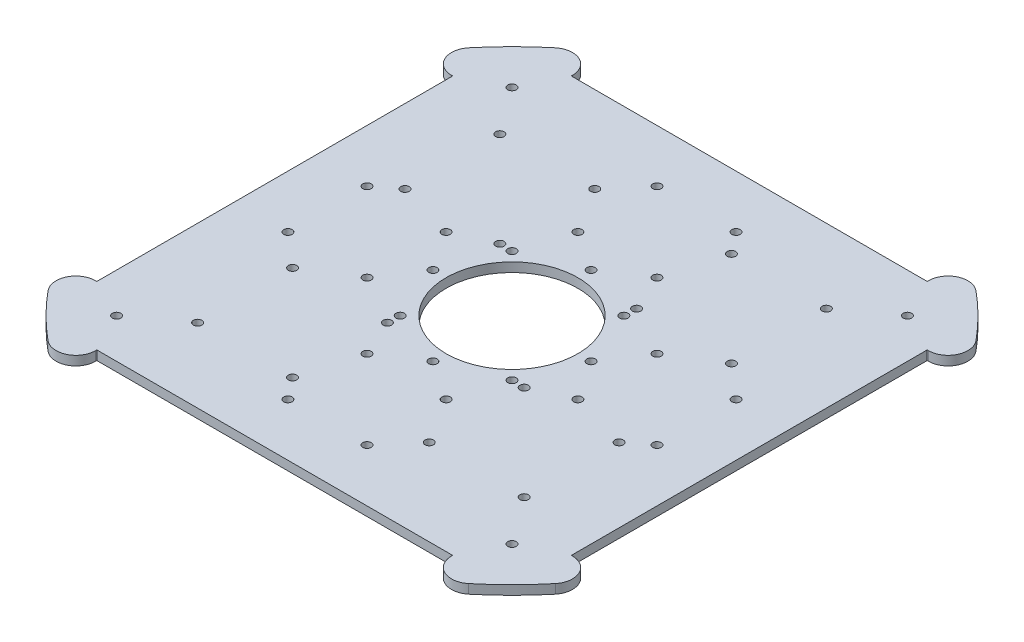
SolidWorks part; units mm, degrees
ref_plane "Front Plane" through (0, 0, 0) normal (0, 0, 1) x (1, 0, 0)
ref_plane "Top Plane" through (0, 0, 0) normal (0, 1, 0) x (1, 0, 0)
ref_plane "Right Plane" through (0, 0, 0) normal (1, 0, 0) x (0, 0, -1)
sketch "Sketch1" plane through (0, 0, 0) normal (0, 1, 0) x (1, 0, 0)
  line L0 (135, 67.5) -> (90, 67.5)
  line L5 (-67.5, 135) -> (67.5, 135)
  line L6 (-67.5, 135) -> (-67.5, 90)
  line L7 (-67.5, 90) -> (67.5, 90)
  line L8 (67.5, 135) -> (67.5, 90)
  line L9 (135, 67.5) -> (135, -67.5)
  line L10 (135, -67.5) -> (90, -67.5)
  line L11 (90, 67.5) -> (90, -67.5)
  line L12 (67.5, -135) -> (67.5, -90)
  line L13 (67.5, -135) -> (-67.5, -135)
  line L14 (-67.5, -135) -> (-67.5, -90)
  line L15 (67.5, -90) -> (-67.5, -90)
  line L16 (-135, -67.5) -> (-90, -67.5)
  line L17 (-135, -67.5) -> (-135, 67.5)
  line L18 (-135, 67.5) -> (-90, 67.5)
  line L19 (-90, -67.5) -> (-90, 67.5)
  line L20 (0, 125) -> (0, 90) construction
  line L21 (0, 135) -> (0, 125) construction
  circle A0 centre (0, 0) radius 125
  point P7 (0, 90)
  point P23 (0, 0)
  dimension "D1" = 250
  dimension "D4" = 35
  dimension "D2" = 135
  dimension "D5" = 10
  dimension "D3" = 4
extrude "Boss-Extrude1" add sketch "Sketch1" along normal blind 3.5 contours L12 A0 L10 L11 L0 L8 L7 L6 L18 L19 L16 L14 L15 region at (0, 0, 0)
fillet "Fillet1" radius 7.5 8 edges at (-105.2081, 1.75, 67.5) (-105.2081, 1.75, -67.5) (-67.5, 1.75, -105.2081) (67.5, 1.75, -105.2081) (105.2081, 1.75, -67.5) (105.2081, 1.75, 67.5) (67.5, 1.75, 105.2081) (-67.5, 1.75, 105.2081)
sketch "Sketch3" plane through (0, 3.5, 0) normal (0, 1, 0) x (1, 0, 0)
  line L0 (0, -90) -> (0, -55) construction
  line L1 (67.5, -90) -> (-67.5, -90) construction
  line L2 (-15, -70) -> (15, -70) construction
  line L3 (-90, 0) -> (-55, 0) construction
  line L4 (-70, 15) -> (-70, -15) construction
  line L5 (0, 90) -> (0, 55) construction
  line L6 (15, 70) -> (-15, 70) construction
  line L7 (90, 0) -> (55, 0) construction
  line L8 (70, -15) -> (70, 15) construction
  line L9 (-90, -67.5) -> (-90, 67.5) construction
  circle A0 centre (-15, -70) radius 1.6
  circle A1 centre (-15, -40) radius 1.6
  circle A2 centre (15, -40) radius 1.6
  circle A3 centre (15, -70) radius 1.6
  circle A4 centre (-40, 15) radius 1.6
  circle A5 centre (-40, -15) radius 1.6
  circle A6 centre (-70, -15) radius 1.6
  circle A7 centre (-70, 15) radius 1.6
  circle A8 centre (15, 40) radius 1.6
  circle A9 centre (-15, 40) radius 1.6
  circle A10 centre (-15, 70) radius 1.6
  circle A11 centre (15, 70) radius 1.6
  circle A12 centre (40, -15) radius 1.6
  circle A13 centre (40, 15) radius 1.6
  circle A14 centre (70, 15) radius 1.6
  circle A15 centre (70, -15) radius 1.6
  point P7 (0, -70)
  point P16 (0, -55)
  point P48 (0, 0)
  dimension "D1" = 3.2
  dimension "D2" = 30
  dimension "D3" = 35
  dimension "D4" = 4
  dimension "D5" = 4
extrude "Cut-Extrude2" cut sketch "Sketch3" against normal through all both and the other way through all
sketch "Sketch4" plane through (0, 3.5, 0) normal (0, 1, 0) x (1, 0, 0)
  circle A0 centre (0, 0) radius 25
  circle A1 centre (0, 30) radius 1.6
  circle A2 centre (21.2132, 21.2132) radius 1.6
  circle A3 centre (30, 0) radius 1.6
  circle A4 centre (21.2132, -21.2132) radius 1.6
  circle A5 centre (0, -30) radius 1.6
  circle A6 centre (-21.2132, -21.2132) radius 1.6
  circle A7 centre (-30, 0) radius 1.6
  circle A8 centre (-21.2132, 21.2132) radius 1.6
  point P22 (0, 0)
  dimension "D1" = 50
  dimension "D2" = 3.2
  dimension "D3" = 30
  dimension "D4" = 8
extrude "Cut-Extrude3" cut sketch "Sketch4" against normal through all both and the other way through all
sketch "Sketch5" plane through (0, 3.5, 0) normal (0, 1, 0) x (1, 0, 0)
  line L0 (75, -75) -> (88.3883, -88.3883) construction
  line L1 (-75, -75) -> (-88.3883, -88.3883) construction
  line L2 (-90, 0) -> (90, 0) construction
  line L3 (-90, -67.5) -> (-90, 67.5) construction
  line L4 (90, 67.5) -> (90, -67.5) construction
  circle A0 centre (75, -75) radius 1.6
  circle A1 centre (-75, -75) radius 1.6
  arc A2 (79.7872, -96.2237) -> (96.2237, -79.7872) centre (0, 0) ccw construction
  arc A3 (-96.2237, -79.7872) -> (-79.7872, -96.2237) centre (0, 0) ccw construction
  circle A9 centre (75, 75) radius 1.6
  circle A10 centre (-75, 75) radius 1.6
  dimension "D1" = 3.2
  dimension "D2" = 150
extrude "Cut-Extrude4" cut sketch "Sketch5" against normal through all both and the other way through all
sketch "Sketch7" plane through (0, 3.5, 0) normal (0, 1, 0) x (1, 0, 0)
  circle A0 centre (25.933, -21.3256) radius 1.6
  circle A1 centre (61.933, -21.3256) radius 1.6
  circle A2 centre (61.933, -57.3256) radius 1.6
  circle A3 centre (25.933, -57.3256) radius 1.6
  point P8 (57.2346, -26.7519)
  point P9 (0, 0)
  point P10 (4, -69.7006)
  point P11 (25.933, -57.3256)
  dimension "D1" = 3.2
  dimension "D2" = 36
  dimension "D3" = 36
  dimension "D4" = 36
  dimension "D5" = 36
extrude "Cut-Extrude6" cut sketch "Sketch7" against normal through all both and the other way through all
pattern_circular "CirPattern2" count 4 over 360 about axis through (0, 3.5, 0) along (0, 1, 0) of "Cut-Extrude6"
